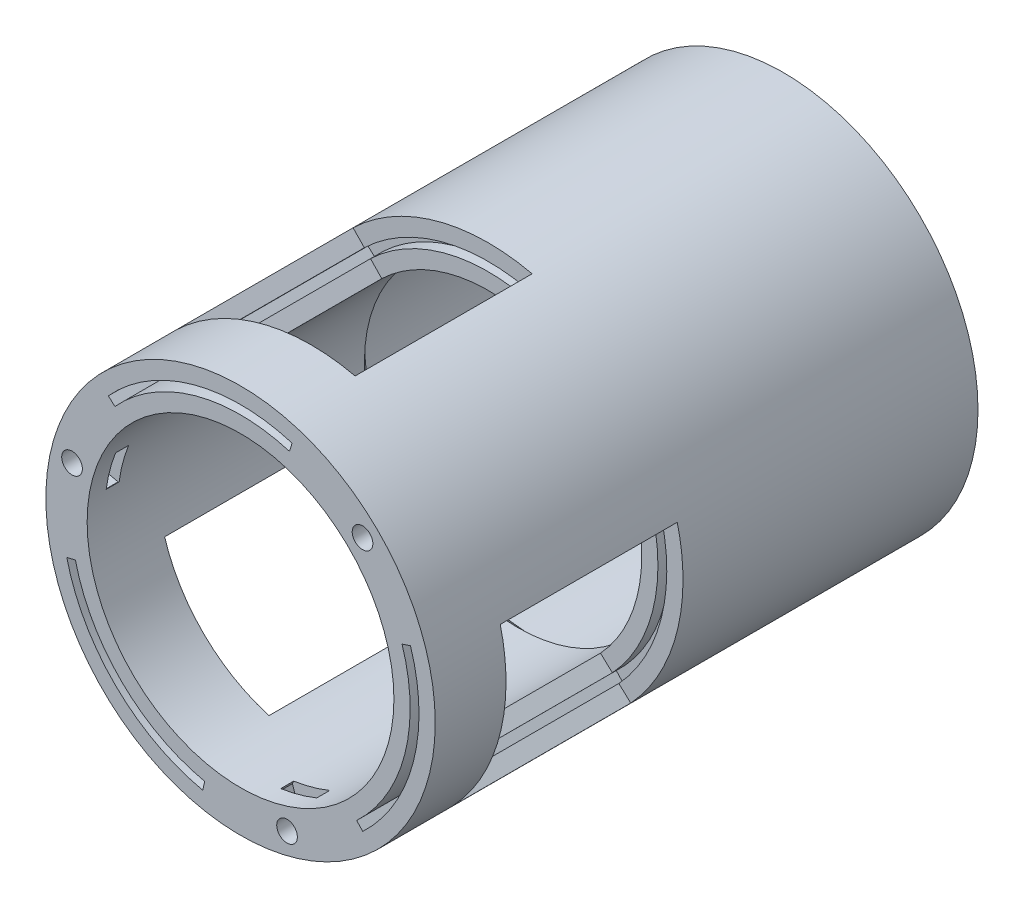
SolidWorks part; units mm, degrees
material "PEI"
ref_plane "Alzado" through (0, 0, 0) normal (0, 0, 1) x (1, 0, 0)
ref_plane "Planta" through (0, 0, 0) normal (0, 1, 0) x (1, 0, 0)
ref_plane "Vista lateral" through (0, 0, 0) normal (1, 0, 0) x (0, 0, -1)
sketch "Croquis1" plane through (0, 0, 0) normal (0, 0, 1) x (1, 0, 0)
  circle A0 centre (0, 0) radius 33
  circle A1 centre (0, 0) radius 29
  dimension "D1" = 66
  dimension "D2" = 4
extrude "Boss-Extrude1" add sketch "Croquis1" along normal blind 92
ref_axis "Eje1" through (0, 0, 92) along (0, 0, -1)
ref_plane "Plano corte lateral" through (0, 0, 0) normal (0.2419, -0.9703, 0) x (0, 0, -1)
sketch "Sketch8" plane through (0, 0, 0) normal (0, 0, -1) x (-1, 0, 0)
  arc A0 (-4, -28.7228) -> (4, -28.7228) centre (0, 0) ccw
  circle A1 centre (0, 0) radius 29 construction
  arc A2 (-4, -28.7228) -> (4, -28.7228) centre (0, -30.3008) cw
  arc A3 (-28.7228, 4) -> (-28.7228, -4) centre (0, 0) ccw
  arc A4 (-28.7228, 4) -> (-28.7228, -4) centre (-30.3008, 0) cw
  arc A5 (4, 28.7228) -> (-4, 28.7228) centre (0, 0) ccw
  arc A6 (4, 28.7228) -> (-4, 28.7228) centre (0, 30.3008) cw
  arc A7 (28.7228, -4) -> (28.7228, 4) centre (0, 0) ccw
  arc A8 (28.7228, -4) -> (28.7228, 4) centre (30.3008, 0) cw
  point P8 (0, -26.0008)
  point P20 (0, 0)
  dimension "D1" = 4.3
  dimension "D2" = 8
  dimension "D3" = 4
extrude "Boss-Extrude4" add sketch "Sketch8" against normal blind 15
sketch "Sketch9" plane through (0, 0, 0) normal (0, 0, -1) x (-1, 0, 0)
  circle A0 centre (0, -29) radius 1.75
  circle A1 centre (0, 0) radius 29 construction
  circle A2 centre (0, 0) radius 33 construction
  circle A3 centre (-29, 0) radius 1.75
  circle A4 centre (0, 29) radius 1.75
  circle A5 centre (29, 0) radius 1.75
  point P16 (0, 0)
  dimension "D1" = 4
  dimension "D2" = 3.5
  dimension "D3" = 4
extrude "Cut-Extrude3" cut sketch "Sketch9" against normal blind 14
ref_plane "Mid plane" through (0, 0, 46) normal (0, 0, 1) x (1, 0, 0)
ref_plane "Plano para USB y Switch" through (-23.3345, -23.3345, 0) normal (-0.7071, -0.7071, 0) x (0, 0, -1)
sketch "Sketch10" plane through (-23.3345, -23.3345, 0) normal (-0.7071, -0.7071, 0) x (0, 0, -1)
  line L0 (0, -33) -> (0, 33) construction
  line L1 (-10.5, 7.5) -> (-3.5, 7.5)
  line L2 (-10.5, 7.5) -> (-10.5, -7.5)
  line L3 (-10.5, -7.5) -> (-3.5, -7.5)
  line L4 (-3.5, 7.5) -> (-3.5, -7.5)
  line L5 (-10.5, 7.5) -> (-3.5, -7.5) construction
  line L6 (-10.5, -7.5) -> (-3.5, 7.5) construction
  line L8 (-45, 6.5) -> (-24, 6.5)
  line L9 (-45, 6.5) -> (-45, -6.5)
  line L10 (-45, -6.5) -> (-24, -6.5)
  line L11 (-24, 6.5) -> (-24, -6.5)
  line L12 (-45, 6.5) -> (-24, -6.5) construction
  line L13 (-45, -6.5) -> (-24, 6.5) construction
  point P0 (-7, 0)
  point P9 (-34.5, 0)
  dimension "D1" = 7
  dimension "D2" = 15
  dimension "D3" = 7
  dimension "D4" = 13
  dimension "D5" = 21
  dimension "D6" = 45
extrude "Corte USB y Switch" cut sketch "Sketch10" against normal blind 10
ref_plane "Plano tuercas superior" through (0, 0, 3) normal (0, 0, -1) x (-1, 0, 0)
sketch "Tuerca" plane through (0, 0, 3) normal (0, 0, -1) x (-1, 0, 0)
  line L30 (-29, -3.4064) -> (-25.5799, -3.4064)
  line L31 (-29, -3.4064) -> (-26.05, -1.7032) construction
  line L32 (-26.05, -1.7032) -> (-26.05, 1.7032) construction
  line L33 (-26.05, 1.7032) -> (-29, 3.4064) construction
  line L34 (-29, 3.4064) -> (-31.95, 1.7032)
  line L35 (-31.95, 1.7032) -> (-31.95, -1.7032)
  line L36 (-31.95, -1.7032) -> (-29, -3.4064)
  line L37 (-29, 3.4064) -> (-25.5799, 3.4064)
  circle A10 centre (-29, 0) radius 2.95 construction
  arc A12 (-25.5799, -3.4064) -> (-25.5799, 3.4064) centre (-28.2041, 0) ccw
  dimension "D4" = 5.9
extrude "Alojamiento tuerca" cut sketch "Tuerca" against normal blind 2.2 contours L30 A12 L37 L34 L35 L36 region at (27.8612, 0, 3)
pattern_circular "Alojamientos Tuercas Superior" count 4 over 360 about axis through (0, 0, 0) along (0, 0, 1) of "Alojamiento tuerca"
sketch "Sketch13" plane through (0, 0, 92) normal (0, 0, 1) x (1, 0, 0)
  circle A0 centre (0, 0) radius 29
  circle A1 centre (0, 0) radius 26
  circle A3 centre (0, 0) radius 29 construction
  circle A4 centre (0, 0) radius 33 construction
  dimension "D1" = 52
  dimension "D2" = 7
extrude "Grosor adicional" add sketch "Sketch13" against normal blind 47
sketch "Corte Revolucion" plane through (0, 0, 0) normal (0.2419, -0.9703, 0) x (0, 0, -1)
  line L0 (-80, 33) -> (-80, 25)
  line L2 (-80, 25) -> (-50, 25)
  line L4 (-50, 33) -> (-80, 33)
  line L5 (-97, 29) -> (-42, 29) construction
  line L6 (-92, 33) -> (-92, -33) construction
  line L14 (-50, 25) -> (-50, 33)
  dimension "D1" = 8
  dimension "D6" = 12
revolve "Cut-Revolve3" cut sketch "Corte Revolucion" angle 57 about axis through (0, 0, 92) along (0, 0, -1)
pattern_circular "CirPattern3" count 3 over 360 about axis through (0, 0, 0) along (0, 0, 1) of "Cut-Revolve3"
sketch "Croquis2" plane through (0, 0, 92) normal (0, 0, 1) x (1, 0, 0)
  line L0 (0, 0) -> (-22.4054, 20.3239) construction
  line L1 (0, 0) -> (8.7376, 28.9606) construction
  line L2 (0, 0) -> (-21.0134, 21.76) construction
  line L3 (0, 0) -> (6.8048, 29.4747) construction
  line L4 (8.7376, 28.9606) -> (8.3043, 27.5246)
  line L5 (-22.4054, 20.3239) -> (-21.2944, 19.3161)
  line L6 (20.7118, -22.0473) -> (19.6848, -20.954)
  line L7 (28.8037, 9.2417) -> (27.3754, 8.7834)
  line L8 (7.4234, 32.1542) -> (5.8487, 25.3336) construction
  line L9 (-22.9237, 23.7382) -> (-18.0611, 18.7028) construction
  line L10 (-29.4494, -6.9133) -> (-27.9891, -6.5705)
  line L11 (-6.3983, -29.5656) -> (-6.0811, -28.0995)
  circle A0 centre (0, 0) radius 28.75 construction
  circle A1 centre (0, 0) radius 30.25 construction
  arc A2 (28.8037, 9.2417) -> (20.7118, -22.0473) centre (0, 0) cw
  circle A3 centre (0, 0) radius 29.5 construction
  arc A4 (-22.4054, 20.3239) -> (8.7376, 28.9606) centre (0, 0) cw
  arc A5 (-21.2944, 19.3161) -> (8.3043, 27.5246) centre (0, 0) cw
  arc A6 (27.3754, 8.7834) -> (19.6848, -20.954) centre (0, 0) cw
  arc A7 (-6.3983, -29.5656) -> (-29.4494, -6.9133) centre (0, 0) cw
  arc A8 (-6.0811, -28.0995) -> (-27.9891, -6.5705) centre (0, 0) cw
  circle A13 centre (0, 0) radius 33 construction
  circle A14 centre (0, 0) radius 26 construction
  point P4 (-21.8499, 19.82)
  point P28 (0, 0)
  point P32 (0, 0)
  dimension "D1" = 1.5
  dimension "D2" = 7
  dimension "D6" = 3.5
  dimension "D3" = 2
  dimension "D4" = 2
  dimension "D5" = 3
extrude "Corte postizos" cut sketch "Croquis2" against normal offset from surface (44 mm away) 2 up to face at (-7.4059, 26.7047, 50) offset beyond the face yes
chamfer "Chamfer3" distance 3 angle 45 1 edges at (20.5061, 20.5061, 45)
sketch "Sketch14" plane through (0, 0, 92) normal (0, 0, 1) x (1, 0, 0)
  line L0 (8.3043, 27.5246) -> (0, 0) construction
  line L1 (0, 0) -> (27.3754, 8.7834) construction
  line L2 (0, 0) -> (20.6768, 21.0409) construction
  line L3 (28.8037, 9.2417) -> (27.3754, 8.7834) construction
  line L4 (8.7376, 28.9606) -> (8.3043, 27.5246) construction
  line L5 (0, 0) -> (7.8835, -28.4271) construction
  line L6 (0, 0) -> (-28.5604, 7.3862) construction
  arc A0 (28.0896, 9.0125) -> (8.5209, 28.2426) centre (0, 0) ccw construction
  circle A1 centre (20.6768, 21.0409) radius 1.75
  circle A2 centre (7.8835, -28.4271) radius 1.75
  arc A3 (-6.2397, -28.8326) -> (20.1983, -21.5006) centre (0, 0) ccw construction
  circle A4 centre (-28.5604, 7.3862) radius 1.75
  arc A5 (-21.8499, 19.82) -> (-28.7193, -6.7419) centre (0, 0) ccw construction
  point P21 (15.6241, 4.4801)
  point P25 (0, 0)
  dimension "D3" = 3.5
  dimension "D1" = 55.422
  dimension "D2" = 27.711
extrude "Cut-Extrude6" cut sketch "Sketch14" against normal blind 10
ref_plane "Plano tuercas inferior" through (0, 0, 89) normal (0, 0, 1) x (1, 0, 0)
sketch "Sketch15" plane through (0, 0, 89) normal (0, 0, 1) x (1, 0, 0)
  line L0 (18.1624, 23.3389) -> (15.8551, 20.8143)
  line L1 (18.1624, 23.3389) -> (17.4295, 20.0123) construction
  line L2 (17.4295, 20.0123) -> (19.9439, 17.7143) construction
  line L3 (19.9439, 17.7143) -> (23.1913, 18.7429) construction
  line L4 (23.1913, 18.7429) -> (23.9242, 22.0695)
  line L5 (23.9242, 22.0695) -> (21.4097, 24.3675)
  line L6 (21.4097, 24.3675) -> (18.1624, 23.3389)
  line L7 (23.1913, 18.7429) -> (20.884, 16.2183)
  line L8 (11.1309, -27.3985) -> (10.0982, -24.138)
  line L9 (4.6362, -29.4557) -> (7.1506, -31.7537)
  line L10 (7.1506, -31.7537) -> (10.398, -30.7251)
  line L11 (10.398, -30.7251) -> (11.1309, -27.3985)
  line L12 (4.6362, -29.4557) -> (3.6034, -26.1952)
  line L13 (11.1309, -27.3985) -> (8.6164, -25.1005) construction
  line L14 (8.6164, -25.1005) -> (5.3691, -26.1291) construction
  line L15 (5.3691, -26.1291) -> (4.6362, -29.4557) construction
  line L16 (-29.2933, 4.0596) -> (-25.9532, 3.3238)
  line L17 (-27.8274, 10.7128) -> (-31.0748, 9.6842)
  line L18 (-31.0748, 9.6842) -> (-31.8077, 6.3576)
  line L19 (-31.8077, 6.3576) -> (-29.2933, 4.0596)
  line L20 (-27.8274, 10.7128) -> (-24.4874, 9.9769)
  line L21 (-29.2933, 4.0596) -> (-26.0459, 5.0882) construction
  line L22 (-26.0459, 5.0882) -> (-25.313, 8.4148) construction
  line L23 (-25.313, 8.4148) -> (-27.8274, 10.7128) construction
  circle A0 centre (20.6768, 21.0409) radius 2.95 construction
  arc A1 (15.8551, 20.8143) -> (20.884, 16.2183) centre (20.1399, 20.4534) ccw
  arc A2 (10.0982, -24.138) -> (3.6034, -26.1952) centre (7.6432, -27.6684) ccw
  circle A3 centre (7.8835, -28.4271) radius 2.95 construction
  arc A5 (-25.9532, 3.3238) -> (-24.4874, 9.9769) centre (-27.7831, 7.215) ccw
  circle A6 centre (-28.5604, 7.3862) radius 2.95 construction
  point P38 (0, 0)
  dimension "D1" = 5.9
  dimension "D2" = 240
  dimension "D3" = 240
  dimension "D4" = 210
  dimension "D5" = 240
  dimension "D6" = 3.4201
  dimension "D7" = 3
extrude "Tuercas inferior" cut sketch "Sketch15" against normal blind 2.2
sketch "Sketch16" plane through (0, 0, 0) normal (0, 0, -1) x (-1, 0, 0)
  line L0 (-24.9235, 11.622) -> (-28.0955, 13.1012)
  line L1 (-11.622, 24.9235) -> (-13.1012, 28.0955)
  line L2 (0, 0) -> (-28.0955, 13.1012) construction
  line L3 (0, 0) -> (-13.1012, 28.0955) construction
  line L4 (0, 0) -> (-20.3414, 0) construction
  line L5 (0, 0) -> (0, 16.9855) construction
  arc A0 (-13.1012, 28.0955) -> (-28.0955, 13.1012) centre (0, 0) ccw
  circle A1 centre (0, 0) radius 33 construction
  arc A2 (-11.622, 24.9235) -> (-24.9235, 11.622) centre (0, 0) ccw
  dimension "D6" = 31
  dimension "D2" = 3.5
  dimension "D3" = 25
  dimension "D4" = 25
  dimension "D5" = 40
extrude "Cut-Extrude7" cut sketch "Sketch16" against normal blind 80
equation "\"D6@Croquis2\"=\"D2@Croquis2\"/2"
equation "\"D2@Sketch14\"=\"D1@Sketch14\"/2"
equation "\"D3@Sketch15\"=\"D2@Sketch15\""
equation "\"D5@Sketch15\"=\"D3@Sketch15\""
equation "\"D4@Sketch16\"=\"D3@Sketch16\""
